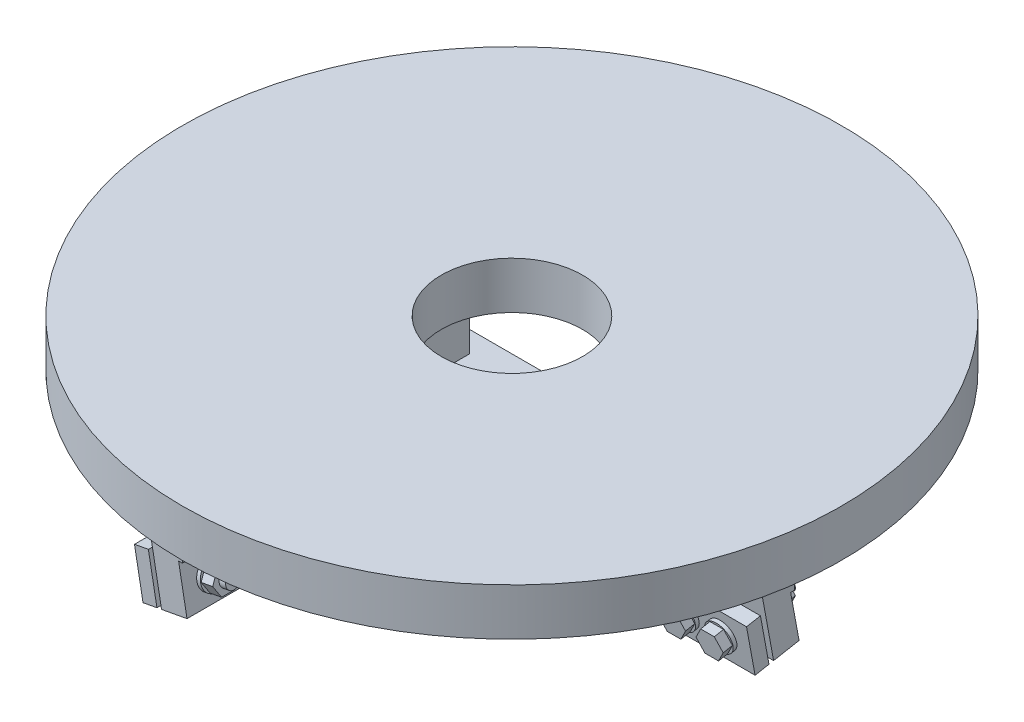
SolidWorks part; units mm, degrees
ref_plane "前视基准面" through (0, 0, 0) normal (0, 0, 1) x (1, 0, 0)
ref_plane "上视基准面" through (0, 0, 0) normal (0, 1, 0) x (1, 0, 0)
ref_plane "右视基准面" through (0, 0, 0) normal (1, 0, 0) x (0, 0, -1)
other "Configuration Table"
sketch "草图1" plane through (0, 0, 0) normal (0, 1, 0) x (1, 0, 0)
  circle A0 centre (0, 0) radius 140
  circle A1 centre (0, 0) radius 30
extrude "Mounting Plate" add sketch "草图1" along normal blind 20 from offset 180
sketch "草图2" plane through (0, 0, 0) normal (0, 0, 1) x (1, 0, 0)
  line L0 (33, 162) -> (47, 162)
  line L1 (47, 162) -> (47, 180)
  line L2 (47, 180) -> (33, 180)
  line L3 (33, 180) -> (33, 162)
extrude "Right Hanger" add sketch "草图2" along normal blind 30 from offset 15
sketch "草图3" plane through (0, 0, 0) normal (0, 0, 1) x (1, 0, 0)
  line L0 (-47, 162) -> (-33, 162)
  line L1 (-33, 162) -> (-33, 180)
  line L2 (-33, 180) -> (-47, 180)
  line L3 (-47, 180) -> (-47, 162)
extrude "Left Hanger" add sketch "草图3" along normal blind 30 from offset 15
sketch "草图4" plane through (0, 0, 0) normal (0, 0, 1) x (1, 0, 0)
  line L0 (-50, 150) -> (50, 150)
  line L1 (50, 150) -> (50, 162)
  line L2 (50, 162) -> (-50, 162)
  line L3 (-50, 162) -> (-50, 150)
extrude "Armature" add sketch "草图4" along normal blind 48 from offset 24
sketch "草图5" plane through (0, 0, 0) normal (0, 0, 1) x (1, 0, 0)
  line L0 (90, 169) -> (130, 169)
  line L1 (130, 169) -> (130, 180)
  line L2 (130, 180) -> (90, 180)
  line L3 (90, 180) -> (90, 169)
extrude "Upper Clamp 1 Bracket" add sketch "草图5" along normal blind 6 from offset 10
sketch "草图6" plane through (0, 0, 0) normal (1, 0, 0) x (0, 0, -1)
  line L0 (-8.0238, 149.5608) -> (-13.2887, 178.0789)
  line L1 (-13.2887, 178.0789) -> (-24.1059, 176.0818)
  line L2 (-24.1059, 176.0818) -> (-18.841, 147.5638)
  line L3 (-18.841, 147.5638) -> (-8.0238, 149.5608)
extrude "Upper Clamp 1" add sketch "草图6" along normal blind 40 from offset 90
sketch "草图7" plane through (0, 0, 0) normal (1, 0, 0) x (0, 0, -1)
  line L0 (-20.8078, 147.2007) -> (-24.4387, 166.8683)
  line L1 (-24.4387, 166.8683) -> (-30.339, 165.779)
  line L2 (-30.339, 165.779) -> (-26.7081, 146.1114)
  line L3 (-26.7081, 146.1114) -> (-20.8078, 147.2007)
extrude "Upper Clamp 1 Cap" add sketch "草图7" along normal blind 40 from offset 90 separate body
sketch "草图8" plane through (0, 0.0475, -0.2575) normal (0, -0.1815, 0.9834) x (1, 0, 0)
  circle A0 centre (102, 158.5321) radius 3.3
  circle A1 centre (118, 158.5321) radius 3.3
extrude "Upper Clamp 1 Holes" cut sketch "草图8" against normal mid plane 44
sketch "草图9" plane through (0, 0.0475, -0.2575) normal (0, -0.1815, 0.9834) x (1, 0, 0)
  circle A0 centre (102, 158.5321) radius 3
  circle A1 centre (118, 158.5321) radius 3
extrude "Upper Clamp 1 Bolt Shanks" add sketch "草图9" along normal blind 30 from offset 28.4 separate body
sketch "草图10" plane through (0, 0.0475, -0.2575) normal (0, -0.1815, 0.9834) x (1, 0, 0)
  circle A0 centre (102, 158.5321) radius 6
  circle A1 centre (102, 158.5321) radius 3.2
  circle A2 centre (118, 158.5321) radius 6
  circle A3 centre (118, 158.5321) radius 3.2
extrude "Upper Clamp 1 Front Washers" add sketch "草图10" along normal blind 1.6 separate body
sketch "草图11" plane through (0, 0.0475, -0.2575) normal (0, -0.1815, 0.9834) x (1, 0, 0)
  line L0 (107.7735, 158.5321) -> (104.8868, 163.5321)
  line L1 (104.8868, 163.5321) -> (99.1132, 163.5321)
  line L2 (99.1132, 163.5321) -> (96.2265, 158.5321)
  line L3 (96.2265, 158.5321) -> (99.1132, 153.5321)
  line L4 (99.1132, 153.5321) -> (104.8868, 153.5321)
  line L5 (104.8868, 153.5321) -> (107.7735, 158.5321)
  line L6 (123.7735, 158.5321) -> (120.8868, 163.5321)
  line L7 (120.8868, 163.5321) -> (115.1132, 163.5321)
  line L8 (115.1132, 163.5321) -> (112.2265, 158.5321)
  line L9 (112.2265, 158.5321) -> (115.1132, 153.5321)
  line L10 (115.1132, 153.5321) -> (120.8868, 153.5321)
  line L11 (120.8868, 153.5321) -> (123.7735, 158.5321)
extrude "Upper Clamp 1 Bolt Heads" add sketch "草图11" along normal blind 4 from offset 1.6 separate body
sketch "草图12" plane through (0, 0.0475, -0.2575) normal (0, -0.1815, 0.9834) x (1, 0, 0)
  circle A0 centre (102, 158.5321) radius 6
  circle A1 centre (102, 158.5321) radius 3.2
  circle A2 centre (118, 158.5321) radius 6
  circle A3 centre (118, 158.5321) radius 3.2
extrude "Upper Clamp 1 Rear Washers" add sketch "草图12" along normal blind 1.6 from offset 20.6 separate body
sketch "草图13" plane through (0, 0.0475, -0.2575) normal (0, -0.1815, 0.9834) x (1, 0, 0)
  line L0 (107.7735, 158.5321) -> (104.8868, 163.5321)
  line L1 (104.8868, 163.5321) -> (99.1132, 163.5321)
  line L2 (99.1132, 163.5321) -> (96.2265, 158.5321)
  line L3 (96.2265, 158.5321) -> (99.1132, 153.5321)
  line L4 (99.1132, 153.5321) -> (104.8868, 153.5321)
  line L5 (104.8868, 153.5321) -> (107.7735, 158.5321)
  line L6 (123.7735, 158.5321) -> (120.8868, 163.5321)
  line L7 (120.8868, 163.5321) -> (115.1132, 163.5321)
  line L8 (115.1132, 163.5321) -> (112.2265, 158.5321)
  line L9 (112.2265, 158.5321) -> (115.1132, 153.5321)
  line L10 (115.1132, 153.5321) -> (120.8868, 153.5321)
  line L11 (120.8868, 153.5321) -> (123.7735, 158.5321)
  circle A0 centre (102, 158.5321) radius 3
  circle A1 centre (118, 158.5321) radius 3
extrude "Upper Clamp 1 Nuts" add sketch "草图13" along normal blind 5 from offset 25.6 separate body
sketch "草图14" plane through (0, 0, 0) normal (0, 0, 1) x (1, 0, 0)
  line L0 (-16, 169) -> (-10, 169)
  line L1 (-10, 169) -> (-10, 180)
  line L2 (-10, 180) -> (-16, 180)
  line L3 (-16, 180) -> (-16, 169)
extrude "Upper Clamp 2 Bracket" add sketch "草图14" along normal blind 40 from offset 90
sketch "草图15" plane through (0, 0, 0) normal (0, 0, 1) x (1, 0, 0)
  line L0 (-8.0238, 149.5608) -> (-13.2887, 178.0789)
  line L1 (-13.2887, 178.0789) -> (-24.1059, 176.0818)
  line L2 (-24.1059, 176.0818) -> (-18.841, 147.5638)
  line L3 (-18.841, 147.5638) -> (-8.0238, 149.5608)
extrude "Upper Clamp 2" add sketch "草图15" along normal blind 40 from offset 90
sketch "草图16" plane through (0, 0, 0) normal (0, 0, 1) x (1, 0, 0)
  line L0 (-20.8078, 147.2007) -> (-24.4387, 166.8683)
  line L1 (-24.4387, 166.8683) -> (-30.339, 165.779)
  line L2 (-30.339, 165.779) -> (-26.7081, 146.1114)
  line L3 (-26.7081, 146.1114) -> (-20.8078, 147.2007)
extrude "Upper Clamp 2 Cap" add sketch "草图16" along normal blind 40 from offset 90 separate body
sketch "草图17" plane through (0.2575, 0.0475, 0) normal (-0.9834, -0.1815, 0) x (0, 0, 1)
  circle A0 centre (102, 158.5321) radius 3.3
  circle A1 centre (118, 158.5321) radius 3.3
extrude "Upper Clamp 2 Holes" cut sketch "草图17" against normal mid plane 44
sketch "草图18" plane through (0.2575, 0.0475, 0) normal (-0.9834, -0.1815, 0) x (0, 0, 1)
  circle A0 centre (102, 158.5321) radius 3
  circle A1 centre (118, 158.5321) radius 3
extrude "Upper Clamp 2 Bolt Shanks" add sketch "草图18" along normal blind 30 from offset 28.4 separate body
sketch "草图19" plane through (0.2575, 0.0475, 0) normal (-0.9834, -0.1815, 0) x (0, 0, 1)
  circle A0 centre (102, 158.5321) radius 6
  circle A1 centre (102, 158.5321) radius 3.2
  circle A2 centre (118, 158.5321) radius 6
  circle A3 centre (118, 158.5321) radius 3.2
extrude "Upper Clamp 2 Front Washers" add sketch "草图19" along normal blind 1.6 separate body
sketch "草图20" plane through (0.2575, 0.0475, 0) normal (-0.9834, -0.1815, 0) x (0, 0, 1)
  line L0 (107.7735, 158.5321) -> (104.8868, 163.5321)
  line L1 (104.8868, 163.5321) -> (99.1132, 163.5321)
  line L2 (99.1132, 163.5321) -> (96.2265, 158.5321)
  line L3 (96.2265, 158.5321) -> (99.1132, 153.5321)
  line L4 (99.1132, 153.5321) -> (104.8868, 153.5321)
  line L5 (104.8868, 153.5321) -> (107.7735, 158.5321)
  line L6 (123.7735, 158.5321) -> (120.8868, 163.5321)
  line L7 (120.8868, 163.5321) -> (115.1132, 163.5321)
  line L8 (115.1132, 163.5321) -> (112.2265, 158.5321)
  line L9 (112.2265, 158.5321) -> (115.1132, 153.5321)
  line L10 (115.1132, 153.5321) -> (120.8868, 153.5321)
  line L11 (120.8868, 153.5321) -> (123.7735, 158.5321)
extrude "Upper Clamp 2 Bolt Heads" add sketch "草图20" along normal blind 4 from offset 1.6 separate body
sketch "草图21" plane through (0.2575, 0.0475, 0) normal (-0.9834, -0.1815, 0) x (0, 0, 1)
  circle A0 centre (102, 158.5321) radius 6
  circle A1 centre (102, 158.5321) radius 3.2
  circle A2 centre (118, 158.5321) radius 6
  circle A3 centre (118, 158.5321) radius 3.2
extrude "Upper Clamp 2 Rear Washers" add sketch "草图21" along normal blind 1.6 from offset 20.6 separate body
sketch "草图22" plane through (0.2575, 0.0475, 0) normal (-0.9834, -0.1815, 0) x (0, 0, 1)
  line L0 (107.7735, 158.5321) -> (104.8868, 163.5321)
  line L1 (104.8868, 163.5321) -> (99.1132, 163.5321)
  line L2 (99.1132, 163.5321) -> (96.2265, 158.5321)
  line L3 (96.2265, 158.5321) -> (99.1132, 153.5321)
  line L4 (99.1132, 153.5321) -> (104.8868, 153.5321)
  line L5 (104.8868, 153.5321) -> (107.7735, 158.5321)
  line L6 (123.7735, 158.5321) -> (120.8868, 163.5321)
  line L7 (120.8868, 163.5321) -> (115.1132, 163.5321)
  line L8 (115.1132, 163.5321) -> (112.2265, 158.5321)
  line L9 (112.2265, 158.5321) -> (115.1132, 153.5321)
  line L10 (115.1132, 153.5321) -> (120.8868, 153.5321)
  line L11 (120.8868, 153.5321) -> (123.7735, 158.5321)
  circle A0 centre (102, 158.5321) radius 3
  circle A1 centre (118, 158.5321) radius 3
extrude "Upper Clamp 2 Nuts" add sketch "草图22" along normal blind 5 from offset 25.6 separate body
sketch "草图23" plane through (0, 0, 0) normal (0, 0, 1) x (1, 0, 0)
  line L0 (-130, 169) -> (-90, 169)
  line L1 (-90, 169) -> (-90, 180)
  line L2 (-90, 180) -> (-130, 180)
  line L3 (-130, 180) -> (-130, 169)
extrude "Upper Clamp 3 Bracket" add sketch "草图23" along normal blind 6 from offset 16
sketch "草图24" plane through (0, 0, 0) normal (1, 0, 0) x (0, 0, -1)
  line L0 (8.0238, 149.5608) -> (13.2887, 178.0789)
  line L1 (13.2887, 178.0789) -> (24.1059, 176.0818)
  line L2 (24.1059, 176.0818) -> (18.841, 147.5638)
  line L3 (18.841, 147.5638) -> (8.0238, 149.5608)
extrude "Upper Clamp 3" add sketch "草图24" along normal blind 40 from offset 130
sketch "草图25" plane through (0, 0, 0) normal (1, 0, 0) x (0, 0, -1)
  line L0 (20.8078, 147.2007) -> (24.4387, 166.8683)
  line L1 (24.4387, 166.8683) -> (30.339, 165.779)
  line L2 (30.339, 165.779) -> (26.7081, 146.1114)
  line L3 (26.7081, 146.1114) -> (20.8078, 147.2007)
extrude "Upper Clamp 3 Cap" add sketch "草图25" along normal blind 40 from offset 130 separate body
sketch "草图26" plane through (0, 0.0475, 0.2575) normal (0, -0.1815, -0.9834) x (-1, 0, 0)
  circle A0 centre (102, 158.5321) radius 3.3
  circle A1 centre (118, 158.5321) radius 3.3
extrude "Upper Clamp 3 Holes" cut sketch "草图26" against normal mid plane 44
sketch "草图27" plane through (0, 0.0475, 0.2575) normal (0, -0.1815, -0.9834) x (-1, 0, 0)
  circle A0 centre (102, 158.5321) radius 3
  circle A1 centre (118, 158.5321) radius 3
extrude "Upper Clamp 3 Bolt Shanks" add sketch "草图27" along normal blind 30 from offset 28.4 separate body
sketch "草图28" plane through (0, 0.0475, 0.2575) normal (0, -0.1815, -0.9834) x (-1, 0, 0)
  circle A0 centre (102, 158.5321) radius 6
  circle A1 centre (102, 158.5321) radius 3.2
  circle A2 centre (118, 158.5321) radius 6
  circle A3 centre (118, 158.5321) radius 3.2
extrude "Upper Clamp 3 Front Washers" add sketch "草图28" along normal blind 1.6 separate body
sketch "草图29" plane through (0, 0.0475, 0.2575) normal (0, -0.1815, -0.9834) x (-1, 0, 0)
  line L0 (107.7735, 158.5321) -> (104.8868, 163.5321)
  line L1 (104.8868, 163.5321) -> (99.1132, 163.5321)
  line L2 (99.1132, 163.5321) -> (96.2265, 158.5321)
  line L3 (96.2265, 158.5321) -> (99.1132, 153.5321)
  line L4 (99.1132, 153.5321) -> (104.8868, 153.5321)
  line L5 (104.8868, 153.5321) -> (107.7735, 158.5321)
  line L6 (123.7735, 158.5321) -> (120.8868, 163.5321)
  line L7 (120.8868, 163.5321) -> (115.1132, 163.5321)
  line L8 (115.1132, 163.5321) -> (112.2265, 158.5321)
  line L9 (112.2265, 158.5321) -> (115.1132, 153.5321)
  line L10 (115.1132, 153.5321) -> (120.8868, 153.5321)
  line L11 (120.8868, 153.5321) -> (123.7735, 158.5321)
extrude "Upper Clamp 3 Bolt Heads" add sketch "草图29" along normal blind 4 from offset 1.6 separate body
sketch "草图30" plane through (0, 0.0475, 0.2575) normal (0, -0.1815, -0.9834) x (-1, 0, 0)
  circle A0 centre (102, 158.5321) radius 6
  circle A1 centre (102, 158.5321) radius 3.2
  circle A2 centre (118, 158.5321) radius 6
  circle A3 centre (118, 158.5321) radius 3.2
extrude "Upper Clamp 3 Rear Washers" add sketch "草图30" along normal blind 1.6 from offset 20.6 separate body
sketch "草图31" plane through (0, 0.0475, 0.2575) normal (0, -0.1815, -0.9834) x (-1, 0, 0)
  line L0 (107.7735, 158.5321) -> (104.8868, 163.5321)
  line L1 (104.8868, 163.5321) -> (99.1132, 163.5321)
  line L2 (99.1132, 163.5321) -> (96.2265, 158.5321)
  line L3 (96.2265, 158.5321) -> (99.1132, 153.5321)
  line L4 (99.1132, 153.5321) -> (104.8868, 153.5321)
  line L5 (104.8868, 153.5321) -> (107.7735, 158.5321)
  line L6 (123.7735, 158.5321) -> (120.8868, 163.5321)
  line L7 (120.8868, 163.5321) -> (115.1132, 163.5321)
  line L8 (115.1132, 163.5321) -> (112.2265, 158.5321)
  line L9 (112.2265, 158.5321) -> (115.1132, 153.5321)
  line L10 (115.1132, 153.5321) -> (120.8868, 153.5321)
  line L11 (120.8868, 153.5321) -> (123.7735, 158.5321)
  circle A0 centre (102, 158.5321) radius 3
  circle A1 centre (118, 158.5321) radius 3
extrude "Upper Clamp 3 Nuts" add sketch "草图31" along normal blind 5 from offset 25.6 separate body
sketch "草图32" plane through (0, 0, 0) normal (0, 0, 1) x (1, 0, 0)
  line L0 (10, 169) -> (16, 169)
  line L1 (16, 169) -> (16, 180)
  line L2 (16, 180) -> (10, 180)
  line L3 (10, 180) -> (10, 169)
extrude "Upper Clamp 4 Bracket" add sketch "草图32" along normal blind 40 from offset 130
sketch "草图33" plane through (0, 0, 0) normal (0, 0, 1) x (1, 0, 0)
  line L0 (8.0238, 149.5608) -> (13.2887, 178.0789)
  line L1 (13.2887, 178.0789) -> (24.1059, 176.0818)
  line L2 (24.1059, 176.0818) -> (18.841, 147.5638)
  line L3 (18.841, 147.5638) -> (8.0238, 149.5608)
extrude "Upper Clamp 4" add sketch "草图33" along normal blind 40 from offset 130
sketch "草图34" plane through (0, 0, 0) normal (0, 0, 1) x (1, 0, 0)
  line L0 (20.8078, 147.2007) -> (24.4387, 166.8683)
  line L1 (24.4387, 166.8683) -> (30.339, 165.779)
  line L2 (30.339, 165.779) -> (26.7081, 146.1114)
  line L3 (26.7081, 146.1114) -> (20.8078, 147.2007)
extrude "Upper Clamp 4 Cap" add sketch "草图34" along normal blind 40 from offset 130 separate body
sketch "草图35" plane through (-0.2575, 0.0475, 0) normal (0.9834, -0.1815, 0) x (0, 0, -1)
  circle A0 centre (102, 158.5321) radius 3.3
  circle A1 centre (118, 158.5321) radius 3.3
extrude "Upper Clamp 4 Holes" cut sketch "草图35" against normal mid plane 44
sketch "草图36" plane through (-0.2575, 0.0475, 0) normal (0.9834, -0.1815, 0) x (0, 0, -1)
  circle A0 centre (102, 158.5321) radius 3
  circle A1 centre (118, 158.5321) radius 3
extrude "Upper Clamp 4 Bolt Shanks" add sketch "草图36" along normal blind 30 from offset 28.4 separate body
sketch "草图37" plane through (-0.2575, 0.0475, 0) normal (0.9834, -0.1815, 0) x (0, 0, -1)
  circle A0 centre (102, 158.5321) radius 6
  circle A1 centre (102, 158.5321) radius 3.2
  circle A2 centre (118, 158.5321) radius 6
  circle A3 centre (118, 158.5321) radius 3.2
extrude "Upper Clamp 4 Front Washers" add sketch "草图37" along normal blind 1.6 separate body
sketch "草图38" plane through (-0.2575, 0.0475, 0) normal (0.9834, -0.1815, 0) x (0, 0, -1)
  line L0 (107.7735, 158.5321) -> (104.8868, 163.5321)
  line L1 (104.8868, 163.5321) -> (99.1132, 163.5321)
  line L2 (99.1132, 163.5321) -> (96.2265, 158.5321)
  line L3 (96.2265, 158.5321) -> (99.1132, 153.5321)
  line L4 (99.1132, 153.5321) -> (104.8868, 153.5321)
  line L5 (104.8868, 153.5321) -> (107.7735, 158.5321)
  line L6 (123.7735, 158.5321) -> (120.8868, 163.5321)
  line L7 (120.8868, 163.5321) -> (115.1132, 163.5321)
  line L8 (115.1132, 163.5321) -> (112.2265, 158.5321)
  line L9 (112.2265, 158.5321) -> (115.1132, 153.5321)
  line L10 (115.1132, 153.5321) -> (120.8868, 153.5321)
  line L11 (120.8868, 153.5321) -> (123.7735, 158.5321)
extrude "Upper Clamp 4 Bolt Heads" add sketch "草图38" along normal blind 4 from offset 1.6 separate body
sketch "草图39" plane through (-0.2575, 0.0475, 0) normal (0.9834, -0.1815, 0) x (0, 0, -1)
  circle A0 centre (102, 158.5321) radius 6
  circle A1 centre (102, 158.5321) radius 3.2
  circle A2 centre (118, 158.5321) radius 6
  circle A3 centre (118, 158.5321) radius 3.2
extrude "Upper Clamp 4 Rear Washers" add sketch "草图39" along normal blind 1.6 from offset 20.6 separate body
sketch "草图40" plane through (-0.2575, 0.0475, 0) normal (0.9834, -0.1815, 0) x (0, 0, -1)
  line L0 (107.7735, 158.5321) -> (104.8868, 163.5321)
  line L1 (104.8868, 163.5321) -> (99.1132, 163.5321)
  line L2 (99.1132, 163.5321) -> (96.2265, 158.5321)
  line L3 (96.2265, 158.5321) -> (99.1132, 153.5321)
  line L4 (99.1132, 153.5321) -> (104.8868, 153.5321)
  line L5 (104.8868, 153.5321) -> (107.7735, 158.5321)
  line L6 (123.7735, 158.5321) -> (120.8868, 163.5321)
  line L7 (120.8868, 163.5321) -> (115.1132, 163.5321)
  line L8 (115.1132, 163.5321) -> (112.2265, 158.5321)
  line L9 (112.2265, 158.5321) -> (115.1132, 153.5321)
  line L10 (115.1132, 153.5321) -> (120.8868, 153.5321)
  line L11 (120.8868, 153.5321) -> (123.7735, 158.5321)
  circle A0 centre (102, 158.5321) radius 3
  circle A1 centre (118, 158.5321) radius 3
extrude "Upper Clamp 4 Nuts" add sketch "草图40" along normal blind 5 from offset 25.6 separate body
